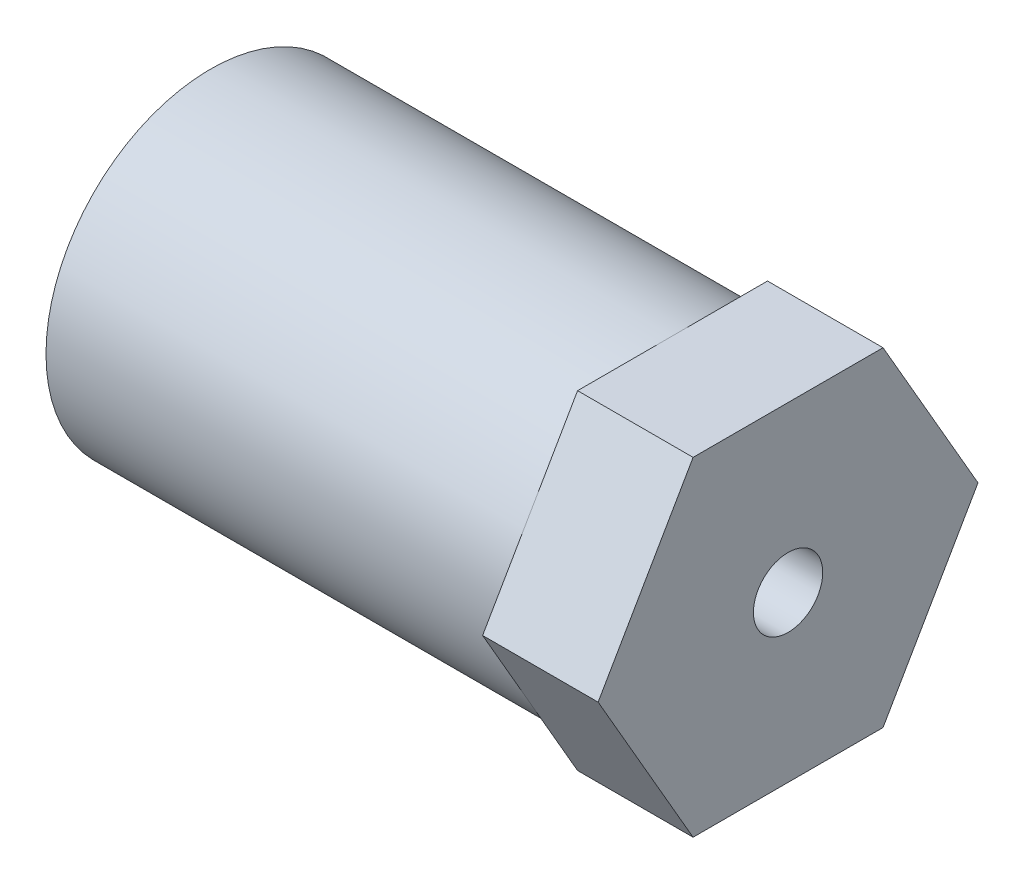
SolidWorks part; units mm, degrees
ref_plane "前视基准面" through (0, 0, 0) normal (0, 0, 1) x (1, 0, 0)
ref_plane "上视基准面" through (0, 0, 0) normal (0, 1, 0) x (1, 0, 0)
ref_plane "右视基准面" through (0, 0, 0) normal (1, 0, 0) x (0, 0, -1)
other "Configuration Table"
sketch "草图1" plane through (0, 0, 0) normal (0, 0, 1) x (1, 0, 0)
  line L0 (-15.977, 0) -> (22.7731, 0) construction
  line L1 (20, 0) -> (20, 7.12)
  line L2 (20, 7.12) -> (0, 7.12)
  line L3 (0, 7.12) -> (0, 0)
  line L4 (0, 0) -> (20, 0)
  line L5 (0, 3) -> (12, 3)
  line L6 (12, 3) -> (12, 0)
  dimension "D1" = 7.12
  dimension "D2" = 20
  dimension "D3" = 3
  dimension "D4" = 12
revolve "旋转1" add sketch "草图1" angle 360 about L0
revolve "切除-旋转1" cut sketch "草图1<4>" angle 360 about L0 region at (6, 1.5, 0)
sketch "草图1<4>" plane through (0, 0, 0) normal (0, 0, 1) x (1, 0, 0) same geometry as "草图1"
sketch "草图2" plane through (20, 0, 0) normal (1, 0, 0) x (0, 0, -1)
  line L1 (8.2215, 0) -> (4.1107, 7.12)
  line L2 (4.1107, 7.12) -> (-4.1107, 7.12)
  line L3 (-4.1107, 7.12) -> (-8.2215, 0)
  line L4 (-8.2215, 0) -> (-4.1107, -7.12)
  line L5 (-4.1107, -7.12) -> (4.1107, -7.12)
  line L6 (4.1107, -7.12) -> (8.2215, 0)
  circle A1 centre (0, 0) radius 7.12 construction
  circle A2 centre (0, 0) radius 7.12 construction
extrude "凸台-拉伸1" add sketch "草图2" along normal blind 5
sketch "草图3" plane through (25, 0, 0) normal (1, 0, 0) x (0, 0, -1)
  circle A0 centre (0, 0) radius 1.5
  dimension "D1" = 3
extrude "切除-拉伸1" cut sketch "草图3" against normal through all and the other way through all
